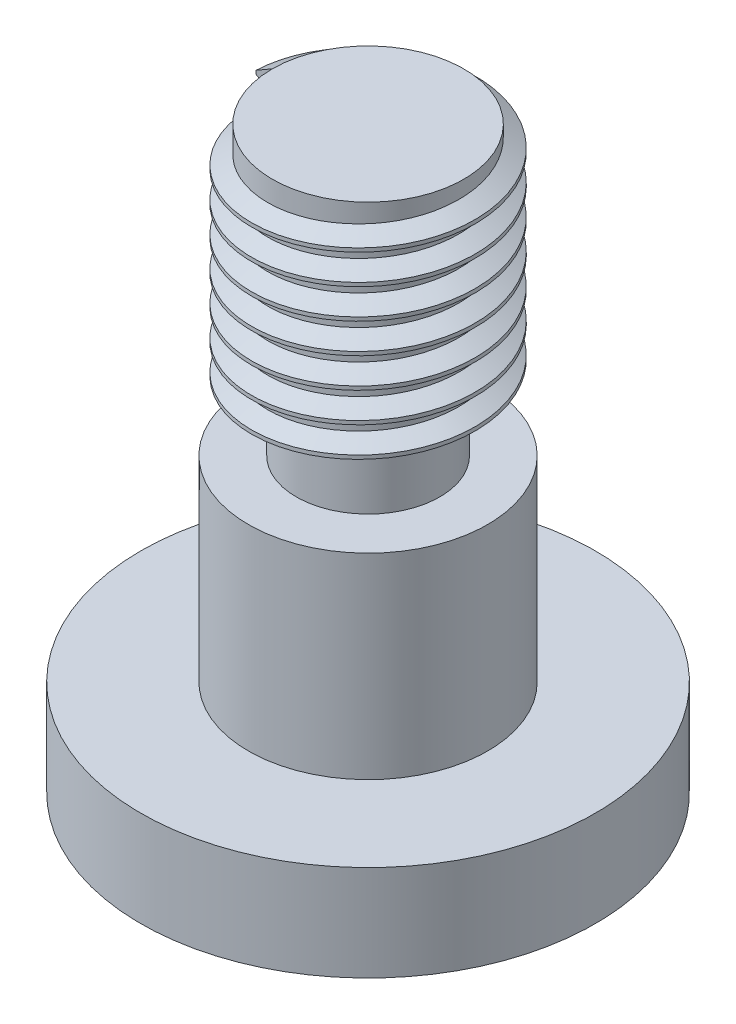
SolidWorks part; units mm, degrees
material "1.4305 (X8CrNiS18-9)"
ref_plane "Ebene vorne" through (0, 0, 0) normal (0, 0, 1) x (1, 0, 0)
ref_plane "Ebene oben" through (0, 0, 0) normal (0, 1, 0) x (1, 0, 0)
ref_plane "Ebene rechts" through (0, 0, 0) normal (1, 0, 0) x (0, 0, -1)
sketch "Sketch1" plane through (0, 0, 0) normal (0, 0, 1) x (1, 0, 0)
  line L0 (0, 24.2) -> (-4, 24.2)
  line L1 (-4, 24.2) -> (-4, 15.2)
  line L2 (-4, 15.2) -> (-3, 15.2)
  line L3 (-3, 15.2) -> (-3, 12.2)
  line L4 (-3, 12.2) -> (-5, 12.2)
  line L5 (-5, 12.2) -> (-5, 4)
  line L6 (-5, 4) -> (-9.5, 4)
  line L7 (-9.5, 4) -> (-9.5, 0)
  line L8 (-9.5, 0) -> (0, 0)
  line L9 (0, 24.2) -> (0, 0) construction
  line L10 (0, 24.2) -> (0, 0)
  dimension "D1" = 4
  dimension "D2" = 1
  dimension "D3" = 3
  dimension "D4" = 1
  dimension "D5" = 12
  dimension "D6" = 8.2
  dimension "D7" = 4
  dimension "D8" = 9.5
revolve "Revolve1" add sketch "Sketch1" angle 360 about L9
thread "Thread1" pitch 1.25 method extrude profile "Thread Profile1" start angle 0, offset 0, length 0, pitch 1.25, diameter 8
ref_plane "Plane1" through (-4, 24.2, 0) normal (0, 0, 1) x (-1, 0, 0)
sketch "Thread Profile1" plane through (-4, 24.2, 0) normal (0, 0, 1) x (-1, 0, 0)
  line L0 (0, 0) -> (0, 1.25) construction
  line L1 (0, 0) -> (0.6766, 0.3906)
  line L2 (0.6766, 0.3906) -> (0.6766, 0.5469)
  line L3 (0.6766, 0.5469) -> (0, 0.9375)
  line L4 (0.6766, 0.4687) -> (0, 0.4687) construction
  line L11 (0, 0) -> (0, 0.9375)
  point P2 (0, 0)
  dimension "Pitch" = 1.25
  dimension "Profile_Angle" = 60
  dimension "Profile_Land" = 0.1562
  dimension "Profile_Height" = 0.6766
